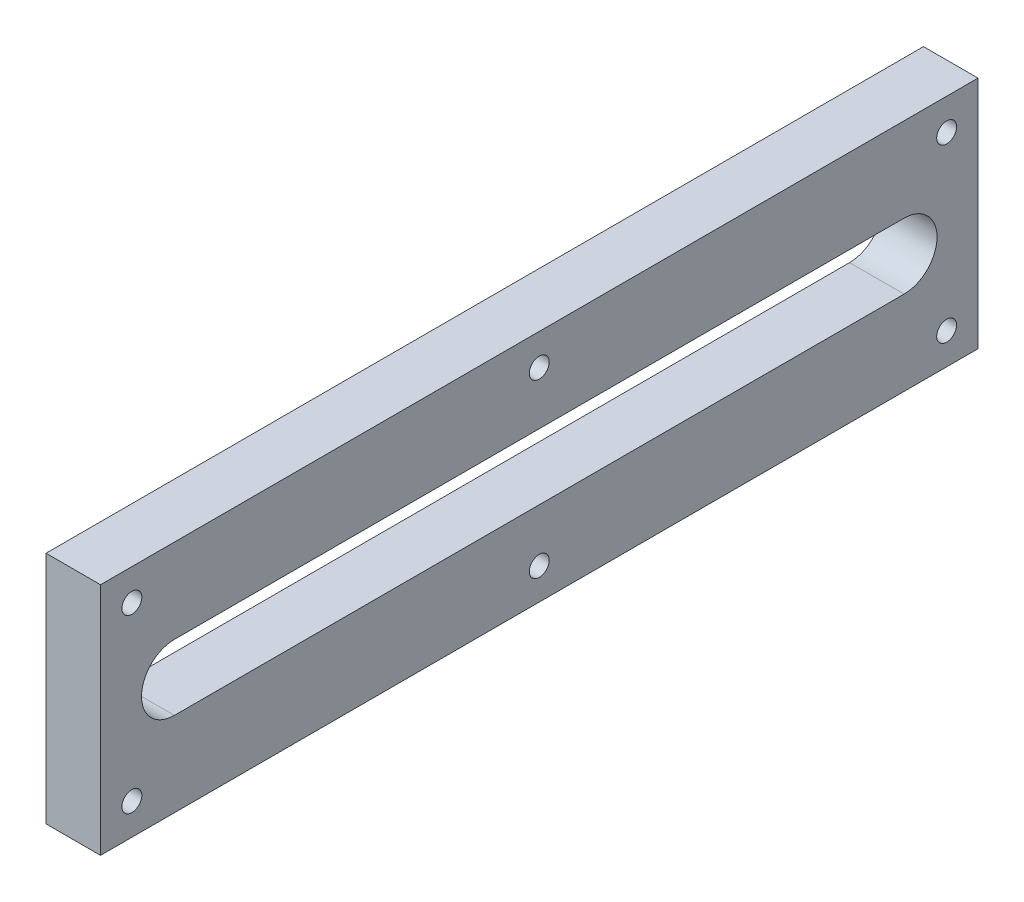
SolidWorks part; units mm, degrees
material "Delrin 2700 NC010, Low Viscosity Acetal Copolymer (SS)"
ref_plane "Front" through (0, 0, 0) normal (0, 0, 1) x (1, 0, 0)
ref_plane "Top" through (0, 0, 0) normal (0, 1, 0) x (1, 0, 0)
ref_plane "Right" through (0, 0, 0) normal (1, 0, 0) x (0, 0, -1)
sketch "Sketch1" plane through (0, 0, 0) normal (1, 0, 0) x (0, 0, -1)
  line L0 (-73.9253, 0) -> (73.9253, 0) construction
  line L1 (88.9, -23.749) -> (-88.9, -23.749)
  line L2 (88.9, -23.749) -> (88.9, 23.749)
  line L3 (88.9, 23.749) -> (-88.9, 23.749)
  line L4 (-88.9, -23.749) -> (-88.9, 23.749)
  line L5 (88.9, -23.749) -> (-88.9, 23.749) construction
  line L6 (88.9, 23.749) -> (-88.9, -23.749) construction
  line L7 (-73.9253, 6.6675) -> (73.9253, 6.6675)
  line L8 (-73.9253, -6.6675) -> (73.9253, -6.6675)
  arc A0 (-73.9253, 6.6675) -> (-73.9253, -6.6675) centre (-73.9253, 0) ccw
  arc A1 (73.9253, -6.6675) -> (73.9253, 6.6675) centre (73.9253, 0) ccw
  point P0 (0, 0)
  point P8 (0, 0)
  dimension "D4" = 13.335
  dimension "D1" = 147.8505
  dimension "D2" = 177.8
  dimension "D3" = 47.498
extrude "Boss-Extrude1" add sketch "Sketch1" along normal blind 11.049
hole_wizard "#10-32 Tapped Hole1" positions "Sketch3" profile "Sketch4" tap size "#10-32" standard "ANSI Inch" end condition through all
sketch "Sketch3" plane through (11.049, 0, 0) normal (1, 0, 0) x (0, 0, -1)
  line L0 (-82.55, 17.399) -> (0, 17.399) construction
  line L1 (0, 17.399) -> (82.55, 17.399) construction
  line L3 (-82.55, 23.749) -> (-82.55, 17.399) construction
  line L4 (88.9, 23.749) -> (-88.9, 23.749) construction
  line L5 (-82.55, 17.399) -> (-82.55, -17.399) construction
  line L6 (-82.55, -17.399) -> (-82.55, -23.749) construction
  line L7 (-88.9, -23.749) -> (88.9, -23.749) construction
  line L8 (-88.9, 23.749) -> (-88.9, -23.749) construction
  point P0 (-82.55, 17.399)
  point P2 (-82.55, -17.399)
  point P4 (0, -17.399)
  point P6 (82.55, -17.399)
  point P8 (82.55, 17.399)
  point P10 (0, 17.399)
  dimension "D1" = 6.35
  dimension "D2" = 6.35
sketch "Sketch4" plane through (11.049, 17.399, 82.55) normal (0, 1, 0) x (0, 0, -1)
  line L0 (0, 0) -> (0, 11.049)
  line L1 (0, 11.049) -> (2.0193, 11.049)
  line L2 (2.0193, 11.049) -> (2.0193, 0)
  line L5 (2.0193, 0) -> (0, 0)
  line L11 (0, -6.35) -> (0, 107.95) construction
  dimension "Thru Tap Drill Dia." = 4.0386
  dimension "Thru Tap Drill Depth" = 11.049
cosmetic thread "Hole Thread1" parameters "D2"=4.826
cosmetic thread "Hole Thread2" parameters "D2"=4.826
cosmetic thread "Hole Thread3" parameters "D2"=4.826
cosmetic thread "Hole Thread4" parameters "D2"=4.826
cosmetic thread "Hole Thread5" parameters "D2"=4.826
cosmetic thread "Hole Thread6" parameters "D2"=4.826
